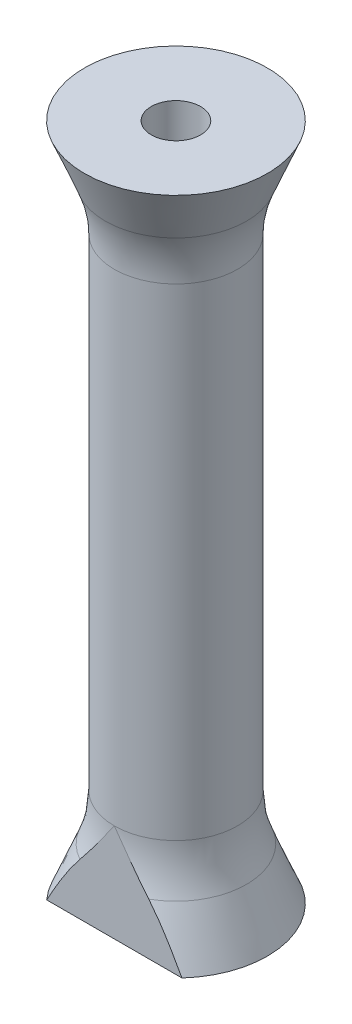
SolidWorks part; units mm, degrees
ref_plane "Front Plane" through (0, 0, 0) normal (0, 0, 1) x (1, 0, 0)
ref_plane "Top Plane" through (0, 0, 0) normal (0, 1, 0) x (1, 0, 0)
ref_plane "Right Plane" through (0, 0, 0) normal (1, 0, 0) x (0, 0, -1)
sketch "Sketch1" plane through (0, 0, 0) normal (0, 1, 0) x (1, 0, 0)
  circle A0 centre (0, 0) radius 6.35
  circle A1 centre (0, 0) radius 2.54
  dimension "D1" = 12.7
  dimension "D2" = 5.08
extrude "Boss-Extrude1" add sketch "Sketch1" along normal blind 69.85
sketch "Sketch2" plane through (0, 0, 0) normal (0, -1, 0) x (-1, 0, 0)
  circle A0 centre (0, 0) radius 9.525
  circle A1 centre (0, 0) radius 2.54
  dimension "D1" = 19.05
extrude "Boss-Extrude2" add sketch "Sketch2" against normal blind 7.62
chamfer "Chamfer1" distance 3.175 angle 68 1 edges at (0, 7.62, -9.525) first distance on face at (0, 7.62, -9.525)
fillet "Fillet1" radius 12.7 1 edges at (0, 7.62, -6.35)
sketch "Sketch3" plane through (0, 69.85, 0) normal (0, 1, 0) x (1, 0, 0)
  circle A0 centre (0, 0) radius 9.525
  circle A1 centre (0, 0) radius 2.54
  dimension "D1" = 19.05
extrude "Boss-Extrude3" add sketch "Sketch3" against normal blind 7.62
chamfer "Chamfer2" distance 3.175 angle 68 1 edges at (0, 62.23, 9.525) first distance on face at (0, 62.23, 9.525)
fillet "Fillet2" radius 12.7 1 edges at (0, 62.23, 6.35)
sketch "Sketch4" plane through (0, 0, 0) normal (0, 0, 1) x (1, 0, 0)
  line L1 (-14.5993, 37.9681) -> (14.5993, 37.9681)
  line L2 (-14.5993, 37.9681) -> (-14.5993, -4.7123)
  line L3 (-14.5993, -4.7123) -> (14.5993, -4.7123)
  line L4 (14.5993, 37.9681) -> (14.5993, -4.7123)
  line L5 (-14.5993, 37.9681) -> (14.5993, -4.7123) construction
  line L6 (-14.5993, -4.7123) -> (14.5993, 37.9681) construction
  point P0 (0, 16.6279)
extrude "Cut-Extrude1" cut sketch "Sketch4" along normal through all from offset 6.35
